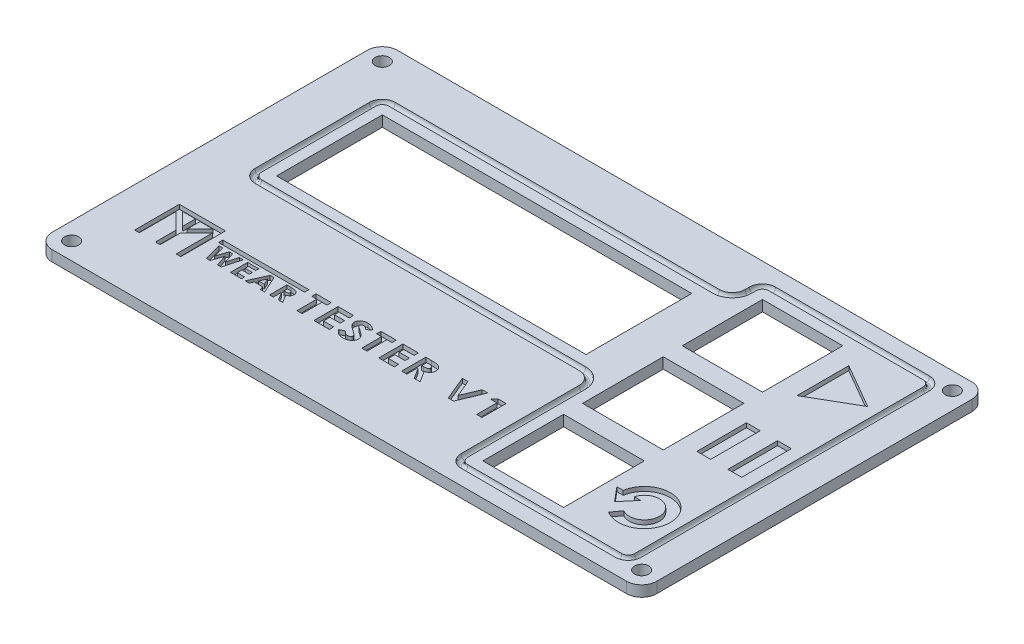
SolidWorks part; units mm, degrees
material "PET"
ref_plane "Front Plane" through (0, 0, 0) normal (0, 0, 1) x (1, 0, 0)
ref_plane "Top Plane" through (0, 0, 0) normal (0, 1, 0) x (1, 0, 0)
ref_plane "Right Plane" through (0, 0, 0) normal (1, 0, 0) x (0, 0, -1)
sketch "Sketch1" plane through (0, 0, 0) normal (0, 1, 0) x (1, 0, 0)
  line L0 (26.05, -9.1) -> (44.15, -9.1)
  line L1 (-55.05, 25) -> (16.05, 25) construction
  line L2 (-55.05, 25) -> (-55.05, 1.1) construction
  line L3 (-55.05, 1.1) -> (16.05, 1.1) construction
  line L4 (16.05, 25) -> (16.05, 1.1) construction
  line L5 (26.05, 14) -> (44.05, 14)
  line L6 (26.05, 14) -> (26.05, 32)
  line L7 (26.05, 32) -> (44.05, 32)
  line L8 (44.05, 14) -> (44.05, 32)
  line L9 (26.05, 14) -> (44.05, 32) construction
  line L10 (26.05, 32) -> (44.05, 14) construction
  line L11 (26.05, -9.1) -> (26.05, 9)
  line L12 (26.05, 9) -> (44.15, 9)
  line L13 (44.15, -9.1) -> (44.15, 9)
  line L14 (26.05, -9.1) -> (44.15, 9) construction
  line L15 (26.05, 9) -> (44.15, -9.1) construction
  line L16 (26.05, -32.2) -> (44.15, -32.2)
  line L17 (26.05, -32.2) -> (26.05, -14.1)
  line L18 (26.05, -14.1) -> (44.15, -14.1)
  line L19 (44.15, -32.2) -> (44.15, -14.1)
  line L20 (26.05, -32.2) -> (44.15, -14.1) construction
  line L21 (26.05, -14.1) -> (44.15, -32.2) construction
  line L22 (47.05, -9) -> (65.05, -9)
  line L23 (47.05, 14) -> (65.05, 14)
  line L24 (47.05, 14) -> (47.05, 32)
  line L25 (47.05, 32) -> (65.05, 32)
  line L26 (65.05, 14) -> (65.05, 32)
  line L27 (47.05, 14) -> (65.05, 32) construction
  line L28 (47.05, 32) -> (65.05, 14) construction
  line L29 (47.05, -9) -> (47.05, 9)
  line L30 (47.05, 9) -> (65.05, 9)
  line L31 (65.05, -9) -> (65.05, 9)
  line L32 (47.05, -9) -> (65.05, 9) construction
  line L33 (47.05, 9) -> (65.05, -9) construction
  line L34 (47.05, -32.1) -> (65.05, -32.1)
  line L35 (47.05, -32.1) -> (47.05, -14.1)
  line L36 (47.05, -14.1) -> (65.05, -14.1)
  line L37 (65.05, -32.1) -> (65.05, -14.1)
  line L38 (47.05, -32.1) -> (65.05, -14.1) construction
  line L39 (47.05, -14.1) -> (65.05, -32.1) construction
  line L40 (-55.35, 25.3) -> (16.35, 25.3)
  line L41 (-70.05, -40) -> (70.05, -40)
  line L42 (-70.05, -40) -> (-70.05, 40)
  line L43 (-70.05, 40) -> (70.05, 40)
  line L44 (70.05, -40) -> (70.05, 40)
  line L45 (-70.05, -40) -> (70.05, 40) construction
  line L46 (-70.05, 40) -> (70.05, -40) construction
  line L48 (-70.05, 0) -> (70.05, 0) construction
  line L50 (16.05, -25) -> (16.05, -1.1) construction
  line L51 (-55.05, -25) -> (16.05, -25) construction
  line L52 (-55.05, -25) -> (-55.05, -1.1) construction
  line L53 (-55.05, -1.1) -> (16.05, -1.1) construction
  line L55 (-59.45, 32.1) -> (20.55, 32.1) construction
  line L56 (-59.45, 32.1) -> (-59.45, -3.9) construction
  line L57 (-59.45, -3.9) -> (20.55, -3.9) construction
  line L58 (20.55, 32.1) -> (20.55, -3.9) construction
  line L60 (16.35, 25.3) -> (16.35, 0.8)
  line L61 (-55.35, 0.8) -> (16.35, 0.8)
  line L62 (-55.35, 25.3) -> (-55.35, 0.8)
  line L63 (25.75, 32.3) -> (44.35, 32.3)
  line L64 (44.35, 13.7) -> (44.35, 32.3)
  line L65 (25.75, 13.7) -> (44.35, 13.7)
  line L66 (25.75, 13.7) -> (25.75, 32.3)
  line L67 (25.75, 9.3) -> (44.45, 9.3)
  line L68 (44.45, -9.4) -> (44.45, 9.3)
  line L69 (25.75, -9.4) -> (44.45, -9.4)
  line L70 (25.75, -9.4) -> (25.75, 9.3)
  line L71 (25.75, -13.8) -> (44.45, -13.8)
  line L72 (44.45, -32.5) -> (44.45, -13.8)
  line L73 (25.75, -32.5) -> (44.45, -32.5)
  line L74 (25.75, -32.5) -> (25.75, -13.8)
  line L76 (-66.05, -36) -> (66.05, -36) construction
  line L77 (-66.05, -36) -> (-66.05, 36) construction
  line L78 (-66.05, 36) -> (66.05, 36) construction
  line L79 (66.05, -36) -> (66.05, 36) construction
  line L80 (-66.05, -36) -> (66.05, 36) construction
  line L81 (-66.05, 36) -> (66.05, -36) construction
  line L82 (-70.05, 40) -> (-85.05, 40)
  line L83 (-70.05, 40) -> (-70.05, -40)
  line L84 (-70.05, -40) -> (-85.05, -40)
  line L85 (-85.05, 40) -> (-85.05, -40)
  circle A0 centre (-66.05, 36) radius 1.65
  circle A1 centre (-66.05, -36) radius 1.65
  circle A2 centre (66.05, -36) radius 1.65
  circle A3 centre (66.05, 36) radius 1.65
  point P4 (35.05, 23)
  point P10 (35.1, -0.05)
  point P15 (35.1, -23.15)
  point P20 (56.05, 23)
  point P25 (56.05, 0)
  point P30 (56.05, -23.1)
  point P35 (0, 0)
  point P66 (0, 0)
  dimension "D25" = 3.3
  dimension "D1" = 71.1
  dimension "D2" = 23.9
  dimension "D3" = 18
  dimension "D4" = 18.1
  dimension "D5" = 18.1
  dimension "D6" = 18
  dimension "D7" = 18
  dimension "D8" = 18
  dimension "D9" = 5
  dimension "D10" = 5
  dimension "D11" = 3
  dimension "D12" = 8
  dimension "D13" = 80
  dimension "D15" = 10
  dimension "D16" = 15
  dimension "D17" = 15
  dimension "D18" = 5
  dimension "D19" = 36
  dimension "D20" = 80
  dimension "D21" = 5
  dimension "D22" = 4.5
  dimension "D26" = 4
  dimension "D24" = 4
  dimension "D27" = 15
  dimension "D14" = 0.3
  dimension "D23" = 0.3
extrude "Boss-Extrude1" add sketch "Sketch1" along normal blind 2.5 contours L41 L44 L43 L42 L69 L70 L67 L68 L37 L34 L35 L36 L31 L22 L29 L30 L26 L23 L24 L25 L62 L40 L60 L61 L65 L66 L63 L64 L73 L74 L71 L72 | L22 L31 L30 L29 | L23 L26 L25 L24 | L34 L37 L36 L35 region at (56.05, 0, 0) region at (56.05, 0, -23) region at (56.05, 0, 23.1) region at (-7.6894, 0, 3.0725)
fillet "Fillet1" radius 3.5 4 edges at (-70.05, 1.25, 40) (70.05, 1.25, 40) (70.05, 1.25, -40) (-70.05, 1.25, -40)
sketch "Sketch2" plane through (0, 2.5, 0) normal (0, 1, 0) x (1, 0, 0)
  line L0 (49.0427, 29) -> (49.0427, 17)
  line L1 (49.0427, 17) -> (59.435, 23)
  line L2 (59.435, 23) -> (49.0427, 29)
  line L3 (55.836, 5.7) -> (59.036, 5.7)
  line L4 (48.636, 5.7) -> (51.836, 5.7)
  line L5 (48.636, 5.7) -> (48.636, -5.8)
  line L6 (48.636, -5.8) -> (51.836, -5.8)
  line L7 (51.836, 5.7) -> (51.836, -5.8)
  line L8 (55.836, 5.7) -> (55.836, -5.8)
  line L9 (55.836, -5.8) -> (59.036, -5.8)
  line L10 (59.036, 5.7) -> (59.036, -5.8)
  line L11 (59.435, 23) -> (52.1492, 23) construction
  line L12 (59.036, -0.05) -> (48.636, -0.05) construction
  line L13 (53.836, 32.2951) -> (53.836, -34.6108) construction
  line L14 (49.2009, -25.4273) -> (46.4509, -22.15)
  line L15 (46.4509, -22.15) -> (47.9199, -22.15)
  line L16 (51.9509, -22.15) -> (49.2009, -25.4273)
  line L17 (57.0474, -22.15) -> (62.8011, -22.15) construction
  line L18 (50.4819, -22.15) -> (51.9509, -22.15)
  line L19 (50.6084, -28.2079) -> (52.085, -26.1805)
  line L20 (25.75, 23) -> (83.5755, 23) construction
  line L21 (25.75, 13.7) -> (25.75, 32.3) construction
  line L22 (25.75, -0.05) -> (86.018, -0.05) construction
  line L23 (25.75, -9.4) -> (25.75, 9.3) construction
  line L24 (25.75, -23.15) -> (93.8874, -23.15) construction
  line L25 (25.75, -32.5) -> (25.75, -13.8) construction
  line L26 (-63.1758, 72.6469) -> (86.8242, 72.6469) construction
  line L31 (-59.35, -0.2) -> (-59.35, 26.3)
  line L32 (-56.35, 29.3) -> (18.75, 29.3)
  line L33 (21.75, 32.3) -> (21.75, 33.3)
  line L34 (24.75, 36.3) -> (60.435, 36.3)
  line L35 (63.435, 33.3) -> (63.435, -33.5)
  line L36 (60.435, -36.5) -> (24.75, -36.5)
  line L37 (21.75, -33.5) -> (21.75, -6.2)
  line L38 (18.75, -3.2) -> (-56.35, -3.2)
  line L39 (-55.35, 25.3) -> (-55.35, 0.8) construction
  line L40 (-55.35, 0.8) -> (16.35, 0.8) construction
  line L41 (-55.5842, -5.7958) -> (-55.5842, -42.6703) construction
  line L42 (-55.35, 25.3) -> (16.35, 25.3) construction
  line L43 (25.75, 32.3) -> (44.35, 32.3) construction
  line L44 (25.75, -32.5) -> (44.45, -32.5) construction
  line L45 (-56.35, 27.8) -> (18.75, 27.8)
  line L46 (23.25, 32.3) -> (23.25, 33.3)
  line L47 (24.75, 34.8) -> (60.435, 34.8)
  line L48 (61.935, 33.3) -> (61.935, -33.5)
  line L49 (60.435, -35) -> (24.75, -35)
  line L50 (23.25, -33.5) -> (23.25, -6.2)
  line L51 (18.75, -1.7) -> (-56.35, -1.7)
  line L52 (-57.85, -0.2) -> (-57.85, 26.3)
  line L53 (-60.9283, -26.5177) -> (-60.9283, -16.1677)
  line L54 (-60.9283, -16.1677) -> (-50.24, -16.1677)
  line L55 (-60.9283, -26.5177) -> (-59.8499, -26.5177)
  line L56 (-59.8499, -26.5177) -> (-59.8499, -18.0492)
  line L57 (-59.8499, -18.0492) -> (-56.1242, -21.7607)
  line L58 (-56.1242, -21.7607) -> (-56.1242, -26.5177)
  line L59 (-56.1242, -26.5177) -> (-55.0442, -26.5177)
  line L60 (-59.1242, -17.2477) -> (-56.1242, -17.2477)
  line L61 (-56.1242, -17.2477) -> (-56.1242, -20.2363)
  line L62 (-56.1242, -20.2363) -> (-59.1242, -17.2477)
  line L63 (-55.0442, -20.2363) -> (-52.0442, -17.2477)
  line L64 (-55.0442, -17.2477) -> (-55.0442, -20.2363)
  line L65 (-52.0442, -17.2477) -> (-55.0442, -17.2477)
  line L66 (-55.0442, -21.7607) -> (-55.0442, -26.5177)
  line L67 (-51.3184, -18.0492) -> (-55.0442, -21.7607)
  line L68 (-51.3184, -26.5177) -> (-51.3184, -18.0492)
  line L69 (-50.24, -26.5177) -> (-51.3184, -26.5177)
  line L70 (-50.24, -26.5177) -> (-50.24, -16.1677)
  line L71 (-50.24, -16.1677) -> (15.8679, -16.1677) construction
  line L72 (-50.24, -26.5177) -> (17.2285, -26.5177) construction
  line L73 (-23.65, -6.2) -> (-23.65, -36) construction
  line L74 (-66.05, -6.2) -> (18.75, -6.2) construction
  line L75 (-66.05, -6.2) -> (-66.05, -36) construction
  line L76 (-66.05, -36) -> (18.75, -36) construction
  line L77 (18.75, -6.2) -> (18.75, -36) construction
  line L78 (-66.05, -21.1) -> (18.75, -21.1) construction
  line L79 (-48.2019, -23.9) -> (-29.2655, -23.9) construction
  line L80 (-48.7019, -18.3) -> (-28.7655, -18.3)
  line L81 (-48.7019, -18.3) -> (-48.7019, -19.3)
  line L82 (-48.7019, -19.3) -> (-28.7655, -19.3)
  line L83 (-28.7655, -18.3) -> (-28.7655, -19.3)
  line L84 (-48.2019, -18.3) -> (-29.2655, -18.3) construction
  line L85 (-27.241, -23.9) -> (18.0219, -23.9) construction
  line L86 (-48.0224, -19.9) -> (-47.1258, -19.9)
  line L87 (-47.1258, -19.9) -> (-46.4327, -22.4537)
  line L88 (-46.4327, -22.4537) -> (-45.5793, -19.9)
  line L89 (-45.5793, -19.9) -> (-44.8213, -19.9)
  line L90 (-44.8213, -19.9) -> (-43.9711, -22.4537)
  line L91 (-43.9711, -22.4537) -> (-43.2796, -19.9)
  line L92 (-43.2796, -19.9) -> (-42.3814, -19.9)
  line L93 (-42.3814, -19.9) -> (-43.4655, -23.9)
  line L94 (-43.4655, -23.9) -> (-44.3405, -23.9)
  line L95 (-44.3405, -23.9) -> (-45.2019, -21.3143)
  line L96 (-45.2019, -21.3143) -> (-46.0657, -23.9)
  line L97 (-46.0657, -23.9) -> (-46.9359, -23.9)
  line L98 (-46.9359, -23.9) -> (-48.0224, -19.9)
  line L99 (-41.3404, -19.9) -> (-38.7763, -19.9)
  line L100 (-38.7763, -19.9) -> (-38.7763, -20.6179)
  line L101 (-38.7763, -20.6179) -> (-40.4686, -20.6179)
  line L102 (-40.4686, -20.6179) -> (-40.4686, -21.3872)
  line L103 (-40.4686, -21.3872) -> (-38.7763, -21.3872)
  line L104 (-38.7763, -21.3872) -> (-38.7763, -22.1051)
  line L105 (-38.7763, -22.1051) -> (-40.4686, -22.1051)
  line L106 (-40.4686, -22.1051) -> (-40.4686, -23.1821)
  line L107 (-40.4686, -23.1821) -> (-38.7763, -23.1821)
  line L108 (-38.7763, -23.1821) -> (-38.7763, -23.9)
  line L109 (-38.7763, -23.9) -> (-41.3404, -23.9)
  line L110 (-41.3404, -23.9) -> (-41.3404, -19.9)
  line L111 (-36.1319, -19.9) -> (-35.2376, -19.9)
  line L112 (-35.2376, -19.9) -> (-33.4275, -23.9)
  line L113 (-33.4275, -23.9) -> (-34.3594, -23.9)
  line L114 (-34.3594, -23.9) -> (-34.7232, -23.0795)
  line L115 (-34.7232, -23.0795) -> (-36.6439, -23.0795)
  line L116 (-36.6439, -23.0795) -> (-37.0077, -23.9)
  line L117 (-37.0077, -23.9) -> (-37.9404, -23.9)
  line L118 (-37.9404, -23.9) -> (-36.1319, -19.9)
  line L119 (-35.6839, -20.9729) -> (-36.3266, -22.3615)
  line L120 (-36.3266, -22.3615) -> (-35.0413, -22.3615)
  line L121 (-35.0413, -22.3615) -> (-35.6839, -20.9729)
  line L122 (-32.2839, -19.9) -> (-31.3256, -19.9)
  line L123 (-30.3617, -22.0747) -> (-29.2327, -23.9)
  line L124 (-29.2327, -23.9) -> (-30.2158, -23.9)
  line L125 (-30.2158, -23.9) -> (-31.2944, -22.1564)
  line L126 (-31.2944, -22.1564) -> (-31.4121, -22.1564)
  line L127 (-31.4121, -22.1564) -> (-31.4121, -23.9)
  line L128 (-31.4121, -23.9) -> (-32.2839, -23.9)
  line L129 (-32.2839, -23.9) -> (-32.2839, -19.9)
  line L130 (-31.4121, -21.4385) -> (-31.1189, -21.4385)
  line L131 (-31.1557, -20.6179) -> (-31.4121, -20.6179)
  line L132 (-31.4121, -20.6179) -> (-31.4121, -21.4385)
  line L133 (-27.0974, -18.3) -> (-23.5794, -18.3)
  line L134 (-23.5794, -18.3) -> (-23.5794, -19.3051)
  line L135 (-23.5794, -19.3051) -> (-24.7281, -19.3051)
  line L136 (-24.7281, -19.3051) -> (-24.7281, -23.9)
  line L137 (-24.7281, -23.9) -> (-25.9487, -23.9)
  line L138 (-25.9487, -23.9) -> (-25.9487, -19.3051)
  line L139 (-25.9487, -19.3051) -> (-27.0974, -19.3051)
  line L140 (-27.0974, -19.3051) -> (-27.0974, -18.3)
  line L141 (-22.0143, -18.3) -> (-18.4246, -18.3)
  line L142 (-18.4246, -18.3) -> (-18.4246, -19.3051)
  line L143 (-18.4246, -19.3051) -> (-20.7938, -19.3051)
  line L144 (-20.7938, -19.3051) -> (-20.7938, -20.3821)
  line L145 (-20.7938, -20.3821) -> (-18.4246, -20.3821)
  line L146 (-18.4246, -20.3821) -> (-18.4246, -21.3872)
  line L147 (-18.4246, -21.3872) -> (-20.7938, -21.3872)
  line L148 (-20.7938, -21.3872) -> (-20.7938, -22.8949)
  line L149 (-20.7938, -22.8949) -> (-18.4246, -22.8949)
  line L150 (-18.4246, -22.8949) -> (-18.4246, -23.9)
  line L151 (-18.4246, -23.9) -> (-22.0143, -23.9)
  line L152 (-22.0143, -23.9) -> (-22.0143, -18.3)
  line L153 (-13.2697, -19.0482) -> (-14.2086, -19.7359)
  line L154 (-17.2902, -22.8511) -> (-16.2245, -22.3205)
  line L155 (-12.0635, -18.3) -> (-8.5456, -18.3)
  line L156 (-8.5456, -18.3) -> (-8.5456, -19.3051)
  line L157 (-8.5456, -19.3051) -> (-9.6943, -19.3051)
  line L158 (-9.6943, -19.3051) -> (-9.6943, -23.9)
  line L159 (-9.6943, -23.9) -> (-10.9148, -23.9)
  line L160 (-10.9148, -23.9) -> (-10.9148, -19.3051)
  line L161 (-10.9148, -19.3051) -> (-12.0635, -19.3051)
  line L162 (-12.0635, -19.3051) -> (-12.0635, -18.3)
  line L163 (-6.9804, -18.3) -> (-3.3907, -18.3)
  line L164 (-3.3907, -18.3) -> (-3.3907, -19.3051)
  line L165 (-3.3907, -19.3051) -> (-5.7599, -19.3051)
  line L166 (-5.7599, -19.3051) -> (-5.7599, -20.3821)
  line L167 (-5.7599, -20.3821) -> (-3.3907, -20.3821)
  line L168 (-3.3907, -20.3821) -> (-3.3907, -21.3872)
  line L169 (-3.3907, -21.3872) -> (-5.7599, -21.3872)
  line L170 (-5.7599, -21.3872) -> (-5.7599, -22.8949)
  line L171 (-5.7599, -22.8949) -> (-3.3907, -22.8949)
  line L172 (-3.3907, -22.8949) -> (-3.3907, -23.9)
  line L173 (-3.3907, -23.9) -> (-6.9804, -23.9)
  line L174 (-6.9804, -23.9) -> (-6.9804, -18.3)
  line L175 (-1.682, -18.3) -> (-0.3403, -18.3)
  line L176 (1.0092, -21.3446) -> (2.5898, -23.9)
  line L177 (2.5898, -23.9) -> (1.2134, -23.9)
  line L178 (1.2134, -23.9) -> (-0.2966, -21.459)
  line L179 (-0.2966, -21.459) -> (-0.4615, -21.459)
  line L180 (-0.4615, -21.459) -> (-0.4615, -23.9)
  line L181 (-0.4615, -23.9) -> (-1.682, -23.9)
  line L182 (-1.682, -23.9) -> (-1.682, -18.3)
  line L183 (-0.4615, -20.4538) -> (-0.0509, -20.4538)
  line L184 (-0.1025, -19.3051) -> (-0.4615, -19.3051)
  line L185 (-0.4615, -19.3051) -> (-0.4615, -20.4538)
  line L186 (6.797, -18.3) -> (8.0871, -18.3)
  line L187 (8.0871, -18.3) -> (9.7406, -22.2779)
  line L188 (9.7406, -22.2779) -> (11.3941, -18.3)
  line L189 (11.3941, -18.3) -> (12.6842, -18.3)
  line L190 (12.6842, -18.3) -> (10.3564, -23.9)
  line L191 (10.3564, -23.9) -> (9.1236, -23.9)
  line L192 (9.1236, -23.9) -> (6.797, -18.3)
  line L193 (15.0256, -18.3) -> (16.9416, -18.3)
  line L194 (16.9416, -18.3) -> (16.9416, -23.9)
  line L195 (16.9416, -23.9) -> (15.7211, -23.9)
  line L196 (15.7211, -23.9) -> (15.7211, -19.2333)
  line L197 (15.7211, -19.2333) -> (14.2852, -19.2333)
  line L198 (14.2852, -19.2333) -> (15.0256, -18.3)
  arc A0 (50.6084, -28.2079) -> (47.9199, -22.15) centre (53.836, -23.15) ccw
  arc A1 (52.085, -26.1805) -> (50.4819, -22.15) centre (53.836, -23.15) ccw
  arc A2 (51.287, -27.2761) -> (53.836, -18.3) centre (53.836, -23.15) ccw construction
  arc A3 (-59.35, 26.3) -> (-56.35, 29.3) centre (-56.35, 26.3) cw
  arc A4 (18.75, 29.3) -> (21.75, 32.3) centre (18.75, 32.3) ccw
  arc A5 (21.75, 33.3) -> (24.75, 36.3) centre (24.75, 33.3) cw
  arc A6 (60.435, 36.3) -> (63.435, 33.3) centre (60.435, 33.3) cw
  arc A7 (63.435, -33.5) -> (60.435, -36.5) centre (60.435, -33.5) cw
  arc A8 (24.75, -36.5) -> (21.75, -33.5) centre (24.75, -33.5) cw
  arc A9 (21.75, -6.2) -> (18.75, -3.2) centre (18.75, -6.2) ccw
  arc A10 (-59.35, -0.2) -> (-56.35, -3.2) centre (-56.35, -0.2) ccw
  arc A11 (18.75, 27.8) -> (23.25, 32.3) centre (18.75, 32.3) ccw
  arc A12 (23.25, 33.3) -> (24.75, 34.8) centre (24.75, 33.3) cw
  arc A13 (60.435, 34.8) -> (61.935, 33.3) centre (60.435, 33.3) cw
  arc A14 (61.935, -33.5) -> (60.435, -35) centre (60.435, -33.5) cw
  arc A15 (24.75, -35) -> (23.25, -33.5) centre (24.75, -33.5) cw
  arc A16 (23.25, -6.2) -> (18.75, -1.7) centre (18.75, -6.2) ccw
  arc A17 (-57.85, -0.2) -> (-56.35, -1.7) centre (-56.35, -0.2) ccw
  arc A18 (-57.85, 26.3) -> (-56.35, 27.8) centre (-56.35, 26.3) cw
  spline S0 degree 3 poles (-31.3256, -19.9) (-31.2038, -19.8994) (-31.0279, -19.9032) (-30.803, -19.9148) (-30.6554, -19.9274) (-30.5223, -19.9441) (-30.4034, -19.9641) (-30.2982, -19.9865) (-30.2057, -20.0144) (-30.1224, -20.0461) (-30.045, -20.0826) (-29.9713, -20.1231) (-29.9021, -20.1691) (-29.8369, -20.2197) (-29.7759, -20.2752) (-29.7188, -20.3355) (-29.6661, -20.4003) (-29.6181, -20.4685) (-29.5769, -20.5408) (-29.5418, -20.6158) (-29.5124, -20.6939) (-29.4913, -20.7754) (-29.4693, -20.8891) (-29.4634, -20.977) (-29.4634, -21.0362) knots 0 0 0 0 0.147269 0.212586 0.272219 0.326243 0.374706 0.418026 0.456127 0.491385 0.525617 0.55958 0.592893 0.626024 0.659167 0.692513 0.726248 0.760105 0.793224 0.826735 0.860141 0.893896 0.928408 1 1 1 1
  spline S1 degree 3 poles (-29.4634, -21.0362) (-29.4631, -21.0981) (-29.4694, -21.1896) (-29.4931, -21.3075) (-29.5184, -21.3904) (-29.5491, -21.4699) (-29.5883, -21.5451) (-29.6337, -21.6163) (-29.6866, -21.6834) (-29.7456, -21.7469) (-29.8131, -21.8054) (-29.8865, -21.861) (-29.9683, -21.9112) (-30.0563, -21.9584) (-30.1862, -22.0179) (-30.2901, -22.0532) (-30.3617, -22.0747) knots 0 0 0 0 0.124686 0.183969 0.241825 0.299057 0.355349 0.412196 0.4689 0.527122 0.586575 0.648431 0.712458 0.779597 0.849396 1 1 1 1
  spline S2 degree 3 poles (-31.1189, -21.4385) (-31.0503, -21.4375) (-30.9511, -21.4371) (-30.8254, -21.4257) (-30.7439, -21.4152) (-30.6711, -21.4034) (-30.6073, -21.386) (-30.5517, -21.3675) (-30.5043, -21.3448) (-30.4641, -21.3185) (-30.4292, -21.289) (-30.4002, -21.2546) (-30.3755, -21.217) (-30.3584, -21.1743) (-30.3391, -21.1117) (-30.335, -21.0609) (-30.3352, -21.0266) knots 0 0 0 0 0.204851 0.295232 0.376365 0.449979 0.515106 0.57331 0.624623 0.67125 0.716446 0.760519 0.804943 0.849927 0.897317 1 1 1 1
  spline S3 degree 3 poles (-30.3352, -21.0266) (-30.3341, -20.9848) (-30.3454, -20.9231) (-30.3802, -20.8477) (-30.4177, -20.7978) (-30.4628, -20.7524) (-30.516, -20.7141) (-30.5761, -20.6825) (-30.6319, -20.6624) (-30.683, -20.6499) (-30.729, -20.6412) (-30.7825, -20.6343) (-30.8429, -20.6278) (-30.9108, -20.6231) (-31.0157, -20.6187) (-31.0983, -20.6185) (-31.1557, -20.6179) knots 0 0 0 0 0.121157 0.179569 0.240198 0.301752 0.365181 0.430195 0.49879 0.537245 0.583128 0.6349 0.694296 0.75975 0.832876 1 1 1 1
  spline S4 degree 3 poles (-14.2086, -19.7359) (-14.2852, -19.6466) (-14.4043, -19.5229) (-14.578, -19.386) (-14.7039, -19.3044) (-14.8305, -19.2405) (-14.9986, -19.1805) (-15.1296, -19.1615) (-15.216, -19.1615) knots 0 0 0 0 0.295304 0.428877 0.553739 0.671168 0.78358 1 1 1 1
  spline S5 degree 3 poles (-15.216, -19.1615) (-15.2921, -19.1613) (-15.4038, -19.1723) (-15.5389, -19.2223) (-15.6238, -19.2711) (-15.6925, -19.3285) (-15.7605, -19.4077) (-15.7819, -19.4812) (-15.7825, -19.5284) knots 0 0 0 0 0.308989 0.447952 0.580945 0.703491 0.808979 1 1 1 1
  spline S6 degree 3 poles (-15.7825, -19.5284) (-15.7842, -19.5763) (-15.7584, -19.6739) (-15.7047, -19.759) (-15.6681, -19.7965) knots 0 0 0 0 0.475944 1 1 1 1
  spline S7 degree 3 poles (-15.6681, -19.7965) (-15.6323, -19.8357) (-15.5629, -19.895) (-15.4575, -19.9822) (-15.3492, -20.0659) (-15.2227, -20.1629) (-15.0132, -20.3144) (-14.8482, -20.4367) (-14.7291, -20.5189) knots 0 0 0 0 0.133977 0.23076 0.34601 0.48035 0.633996 1 1 1 1
  spline S8 degree 3 poles (-14.7291, -20.5189) (-14.6195, -20.5968) (-14.4622, -20.7052) (-14.2673, -20.8462) (-14.1458, -20.931) (-14.045, -21.0074) (-13.9437, -21.0819) (-13.8782, -21.134) (-13.8407, -21.1651) knots 0 0 0 0 0.367089 0.521493 0.656908 0.771457 0.867017 1 1 1 1
  spline S9 degree 3 poles (-13.8407, -21.1651) (-13.7229, -21.2649) (-13.5612, -21.4162) (-13.3847, -21.6348) (-13.2869, -21.7894) (-13.2155, -21.9464) (-13.1439, -22.1628) (-13.1268, -22.3347) (-13.1261, -22.4495) knots 0 0 0 0 0.304367 0.434332 0.552442 0.663491 0.773417 1 1 1 1
  spline S10 degree 3 poles (-13.1261, -22.4495) (-13.1272, -22.5603) (-13.1411, -22.7261) (-13.2029, -22.9351) (-13.2633, -23.0834) (-13.3444, -23.2226) (-13.4406, -23.356) (-13.5569, -23.4798) (-13.6883, -23.5956) (-13.8341, -23.7008) (-13.9916, -23.7933) (-14.1602, -23.8704) (-14.3393, -23.9338) (-14.529, -23.9825) (-14.8021, -24.0318) (-15.0145, -24.0437) (-15.1588, -24.0436) knots 0 0 0 0 0.11537 0.171176 0.225852 0.28135 0.338062 0.396328 0.45742 0.51973 0.582747 0.646876 0.711984 0.779813 0.850057 1 1 1 1
  spline S11 degree 3 poles (-15.1588, -24.0436) (-15.273, -24.0436) (-15.4421, -24.0353) (-15.6625, -24.005) (-15.8199, -23.9737) (-15.9717, -23.9333) (-16.1176, -23.8842) (-16.2575, -23.8251) (-16.3926, -23.7583) (-16.5221, -23.6801) (-16.6468, -23.5928) (-16.766, -23.4944) (-16.8811, -23.3865) (-16.9903, -23.2672) (-17.1343, -23.0935) (-17.2303, -22.9508) (-17.2902, -22.8511) knots 0 0 0 0 0.133395 0.197302 0.259636 0.320637 0.380558 0.439264 0.49784 0.556394 0.615625 0.675497 0.736652 0.79968 0.864191 1 1 1 1
  spline S12 degree 3 poles (-16.2245, -22.3205) (-16.1506, -22.4323) (-16.03, -22.5855) (-15.8481, -22.7582) (-15.7115, -22.8608) (-15.5695, -22.9398) (-15.3748, -23.0161) (-15.22, -23.0384) (-15.1173, -23.0385) knots 0 0 0 0 0.292061 0.422952 0.545866 0.663349 0.776115 1 1 1 1
  spline S13 degree 3 poles (-15.1173, -23.0385) (-15.0159, -23.039) (-14.8676, -23.0205) (-14.6851, -22.953) (-14.5694, -22.8824) (-14.4716, -22.8015) (-14.3777, -22.6834) (-14.345, -22.5776) (-14.3466, -22.5079) knots 0 0 0 0 0.29547 0.430685 0.56414 0.688619 0.798928 1 1 1 1
  spline S14 degree 3 poles (-14.3466, -22.5079) (-14.345, -22.4416) (-14.372, -22.3414) (-14.4416, -22.2168) (-14.5036, -22.1381) (-14.567, -22.072) (-14.6291, -22.0155) (-14.703, -21.9511) (-14.791, -21.8822) (-14.8908, -21.806) (-15.0478, -21.6893) (-15.1751, -21.6031) (-15.2631, -21.542) knots 0 0 0 0 0.142846 0.221999 0.309697 0.360419 0.421544 0.492612 0.573811 0.665086 0.766465 1 1 1 1
  spline S15 degree 3 poles (-15.2631, -21.542) (-15.4316, -21.4271) (-15.6719, -21.259) (-15.9716, -21.0355) (-16.1613, -20.8854) (-16.3265, -20.7462) (-16.4687, -20.619) (-16.5857, -20.5015) (-16.6808, -20.3925) (-16.7569, -20.288) (-16.8232, -20.1867) (-16.8778, -20.0848) (-16.9232, -19.9828) (-16.9596, -19.8814) (-16.9918, -19.7465) (-17.0045, -19.6446) (-17.003, -19.5766) knots 0 0 0 0 0.224706 0.322998 0.411848 0.491073 0.561071 0.621952 0.67365 0.720203 0.764311 0.806888 0.84746 0.887198 0.925366 1 1 1 1
  spline S16 degree 3 poles (-17.003, -19.5766) (-17.0035, -19.4819) (-16.9877, -19.3403) (-16.9315, -19.1605) (-16.8738, -19.0317) (-16.8002, -18.9079) (-16.7086, -18.7904) (-16.6013, -18.6779) (-16.4796, -18.5721) (-16.3457, -18.475) (-16.2022, -18.3898) (-16.0508, -18.3177) (-15.8922, -18.2579) (-15.7258, -18.2122) (-15.4899, -18.1677) (-15.3071, -18.1573) (-15.1835, -18.1564) knots 0 0 0 0 0.110922 0.165527 0.22025 0.275859 0.333966 0.394405 0.45776 0.522707 0.587935 0.653004 0.719007 0.7863 0.854965 1 1 1 1
  spline S17 degree 3 poles (-15.1835, -18.1564) (-15.0213, -18.1567) (-14.779, -18.1803) (-14.4658, -18.2602) (-14.276, -18.3309) (-14.1253, -18.4007) (-14.0096, -18.4638) (-13.892, -18.5375) (-13.7703, -18.6186) (-13.6487, -18.7127) (-13.4778, -18.8526) (-13.3522, -18.9667) (-13.2697, -19.0482) knots 0 0 0 0 0.224009 0.334383 0.445685 0.503229 0.563788 0.627577 0.694912 0.765681 0.839823 1 1 1 1
  spline S18 degree 3 poles (-0.3403, -18.3) (-0.1697, -18.2992) (0.0764, -18.3045) (0.3913, -18.3208) (0.5979, -18.3384) (0.7843, -18.3618) (0.9508, -18.3897) (1.0981, -18.4211) (1.2276, -18.4602) (1.3441, -18.5045) (1.4526, -18.5557) (1.5557, -18.6123) (1.6526, -18.6768) (1.7438, -18.7476) (1.8293, -18.8252) (1.9092, -18.9096) (1.9829, -19.0004) (2.0502, -19.0959) (2.1079, -19.1971) (2.157, -19.3022) (2.1982, -19.4115) (2.2277, -19.5256) (2.2586, -19.6847) (2.2667, -19.8078) (2.2667, -19.8907) knots 0 0 0 0 0.147269 0.212586 0.272219 0.326243 0.374706 0.418026 0.456127 0.491385 0.525617 0.55958 0.592893 0.626024 0.659167 0.692513 0.726248 0.760105 0.793224 0.826735 0.860141 0.893896 0.928408 1 1 1 1
  spline S19 degree 3 poles (2.2667, -19.8907) (2.2671, -19.9774) (2.2583, -20.1054) (2.2252, -20.2705) (2.1897, -20.3866) (2.1467, -20.4979) (2.0919, -20.6031) (2.0283, -20.7028) (1.9543, -20.7967) (1.8717, -20.8857) (1.7772, -20.9675) (1.6744, -21.0454) (1.5599, -21.1157) (1.4368, -21.1818) (1.2548, -21.2651) (1.1094, -21.3145) (1.0092, -21.3446) knots 0 0 0 0 0.124686 0.183969 0.241825 0.299057 0.355349 0.412196 0.4689 0.527122 0.586575 0.648431 0.712458 0.779597 0.849396 1 1 1 1
  spline S20 degree 3 poles (-0.0509, -20.4538) (0.0452, -20.4525) (0.1839, -20.452) (0.3599, -20.436) (0.474, -20.4213) (0.576, -20.4048) (0.6653, -20.3804) (0.7432, -20.3545) (0.8095, -20.3228) (0.8659, -20.2859) (0.9147, -20.2446) (0.9553, -20.1965) (0.9899, -20.1438) (1.0138, -20.084) (1.0408, -19.9964) (1.0465, -19.9253) (1.0462, -19.8772) knots 0 0 0 0 0.204851 0.295232 0.376365 0.449979 0.515106 0.57331 0.624623 0.67125 0.716446 0.760519 0.804943 0.849927 0.897317 1 1 1 1
  spline S21 degree 3 poles (1.0462, -19.8772) (1.0478, -19.8187) (1.032, -19.7324) (0.9832, -19.6268) (0.9308, -19.557) (0.8677, -19.4934) (0.7932, -19.4397) (0.709, -19.3955) (0.6308, -19.3674) (0.5593, -19.3498) (0.495, -19.3377) (0.42, -19.328) (0.3355, -19.3189) (0.2405, -19.3123) (0.0935, -19.3062) (-0.0221, -19.3059) (-0.1025, -19.3051) knots 0 0 0 0 0.121157 0.179569 0.240198 0.301752 0.365181 0.430195 0.49879 0.537245 0.583128 0.6349 0.694296 0.75975 0.832876 1 1 1 1
  point P16 (55.7921, 23)
  point P17 (53.836, -0.05)
  point P27 (49.4767, -21.0243)
  point P68 (21.75, 29.3)
  point P108 (-55.5842, -26.5177)
  point P126 (-55.5842, -16.1677)
  point P145 (32.8271, -24.6)
  point P146 (0, 0)
  point P147 (29.9218, -24.6)
  point P148 (0, 0)
  point P149 (-21.1855, -24.1)
  point P152 (-20.0242, -24.1)
  point P153 (0, 0)
  point P154 (-46.3074, -24.1)
  point P155 (-26.9798, -24.1)
  point P156 (-27.2938, -24.1)
  point P157 (-25.2452, -24.1)
  point P158 (19.7425, -25.7831)
  point P159 (16.5258, -24.1)
  point P160 (19.488, -24.1)
  point P161 (0, 0)
  point P162 (-25.7979, -23.9)
  point P163 (-48.2019, -23.9)
  point P164 (-28.235, -23.9)
  point P165 (-29.0587, -23.9)
  point P166 (-26.641, -23.9)
  point P167 (0, 0)
  point P168 (0, 0)
  point P169 (0, 0)
  point P170 (0, 0)
  point P171 (18.0219, -23.9)
  point P172 (0, 0)
  point P173 (0, 0)
  point P174 (-29.2655, -23.9)
  point P175 (0, 0)
  point P176 (-27.6167, -23.9)
  point P177 (0, 0)
  point P178 (-27.241, -23.9)
  dimension "D8" = 2.5
  dimension "D9" = 1.35
  dimension "D11" = 12
  dimension "D21" = 3
  dimension "D22" = 3
  dimension "D1" = 60
  dimension "D2" = 60
  dimension "D3" = 4
  dimension "D4" = 3.2
  dimension "D5" = 3.2
  dimension "D6" = 12
  dimension "D7" = 11.5
  dimension "D10" = 50
  dimension "D12" = 1
  dimension "D13" = 5.5
  dimension "D14" = 4
  dimension "D15" = 4
  dimension "D16" = 4
  dimension "D17" = 4
  dimension "D18" = 4
  dimension "D19" = 4
  dimension "D20" = 4
  dimension "D24" = 1.0784
  dimension "D25" = 10.35
  dimension "D26" = 5.3441
  dimension "D27" = 1.08
  dimension "D28" = 1.08
  dimension "D29" = 1.08
  dimension "D30" = 2.8
  dimension "D31" = 1
  dimension "D32" = 3
  dimension "D33" = 0.5
  dimension "D34" = 0.5
  dimension "D23" = 1.5
extrude "Cut-Extrude2" cut sketch "Sketch2" against normal blind 1 contours L69 L70 L54 L53 L55 L56 L57 L58 L59 L66 L67 L68 L61 L62 L60 L65 L63 L64 | L98 L97 L96 L95 L94 L93 L92 L91 L90 L89 L88 L87 L86 | L83 L80 L81 L82 | L118 L117 L116 L115 L114 L113 L112 L111 L121 L120 L119 | L110 L109 L108 L107 L106 L105 L104 L103 L102 L101 L100 L99 | S1 S0 L122 L129 L128 L127 L126 L125 L124 L123 S3 S2 L130 L132 L131 | L140 L139 L138 L137 L136 L135 L134 L133 | L152 L151 L150 L149 L148 L147 L146 L145 L144 L143 L142 L141 | S17 S16 S15 S14 S13 S12 L154 S11 S10 S9 S8 S7 S6 S5 S4 L153 | L162 L161 L160 L159 L158 L157 L156 L155 | L174 L173 L172 L171 L170 L169 L168 L167 L166 L165 L164 L163 | S19 S18 L175 L182 L181 L180 L179 L178 L177 L176 S21 S20 L183 L185 L184 | L192 L191 L190 L189 L188 L187 L186 | L198 L197 L196 L195 L194 L193 | A1 L19 A0 L15 L14 L16 L18 | L7 L4 L5 L6 | L10 L3 L8 L9 | L1 L2 L0 | L31 A10 L38 A9 L37 A8 L36 A7 L35 A6 L34 A5 L33 A4 L32 A3 L52 A18 L45 A11 L46 A12 L47 A13 L48 A14 L49 A15 L50 A16 L51 A17 region at (52.5068, 2.5, -23) region at (57.436, 2.5, 0.05) region at (50.236, 2.5, 0.05) region at (47.9636, 2.5, 23.6731) region at (-57.9226, 2.5, -13.05) region at (-55.5842, 2.5, 20.197) region at (-38.7337, 2.5, 18.8) region at (-47.5741, 2.5, 19.9692) region at (-40.2492, 2.5, 21.8738) region at (-35.6847, 2.5, 19.9603) region at (-31.0065, 2.5, 21.8206) region at (-25.3384, 2.5, 20.5198) region at (-20.4867, 2.5, 21.0633) region at (-15.1198, 2.5, 21.1716) region at (-10.3046, 2.5, 20.5198) region at (-5.4529, 2.5, 21.0633) region at (0.1064, 2.5, 20.9888) region at (7.442, 2.5, 18.3813) region at (16.1834, 2.5, 20.8104)
fillet "Fillet2" radius 0.6 16 edges at (42.5925, 1.5, 36.5) (22.6287, 1.5, 35.6213) (62.5563, 1.5, 35.6213) (21.75, 1.5, 19.85) (63.435, 1.5, 0.1) (20.8713, 1.5, 4.0787) (62.5563, 1.5, -35.4213) (-18.8, 1.5, 3.2) (42.5925, 1.5, -36.3) (-58.4713, 1.5, 2.3213) (22.6287, 1.5, -35.4213) (-59.35, 1.5, -13.05) (21.75, 1.5, -32.8) (-58.4713, 1.5, -28.4213) (20.8713, 1.5, -30.1787) (-18.8, 1.5, -29.3) second distance 1 first distance on face at (11.8963, 1.5, -6.475)
fillet "Fillet3" radius 1 16 edges at (42.5925, 1.5, 35) (23.6893, 1.5, 34.5607) (61.4957, 1.5, 34.5607) (23.25, 1.5, 19.85) (61.935, 1.5, 0.1) (21.932, 1.5, 3.018) (61.4957, 1.5, -34.3607) (-18.8, 1.5, 1.7) (42.5925, 1.5, -34.8) (-57.4107, 1.5, 1.2607) (23.6893, 1.5, -34.3607) (-57.85, 1.5, -13.05) (23.25, 1.5, -32.8) (-57.4107, 1.5, -27.3607) (21.932, 1.5, -29.118) (-18.8, 1.5, -27.8) second distance 0.6 first distance on face at (42.5925, 2, 35) first distance on face at (23.8447, 2, 34.4053) first distance on face at (61.3404, 2, 34.4053) first distance on face at (23.25, 2, 19.85) first distance on face at (61.935, 2, 0.1) first distance on face at (21.466, 2, 3.484) first distance on face at (61.3404, 2, -34.2053) first distance on face at (-18.8, 2, 1.7) first distance on face at (42.5925, 2, -34.8) first distance on face at (-57.2553, 2, 1.1053) first distance on face at (23.8447, 2, -34.2053) first distance on face at (-57.85, 2, -13.05) first distance on face at (23.25, 2, -32.8) first distance on face at (-57.2553, 2, -27.2053) first distance on face at (21.466, 2, -29.584) first distance on face at (-18.8, 2, -27.8)
equation "\"width\"= 80"
equation "\"D13@Sketch1\"=\"width\""
